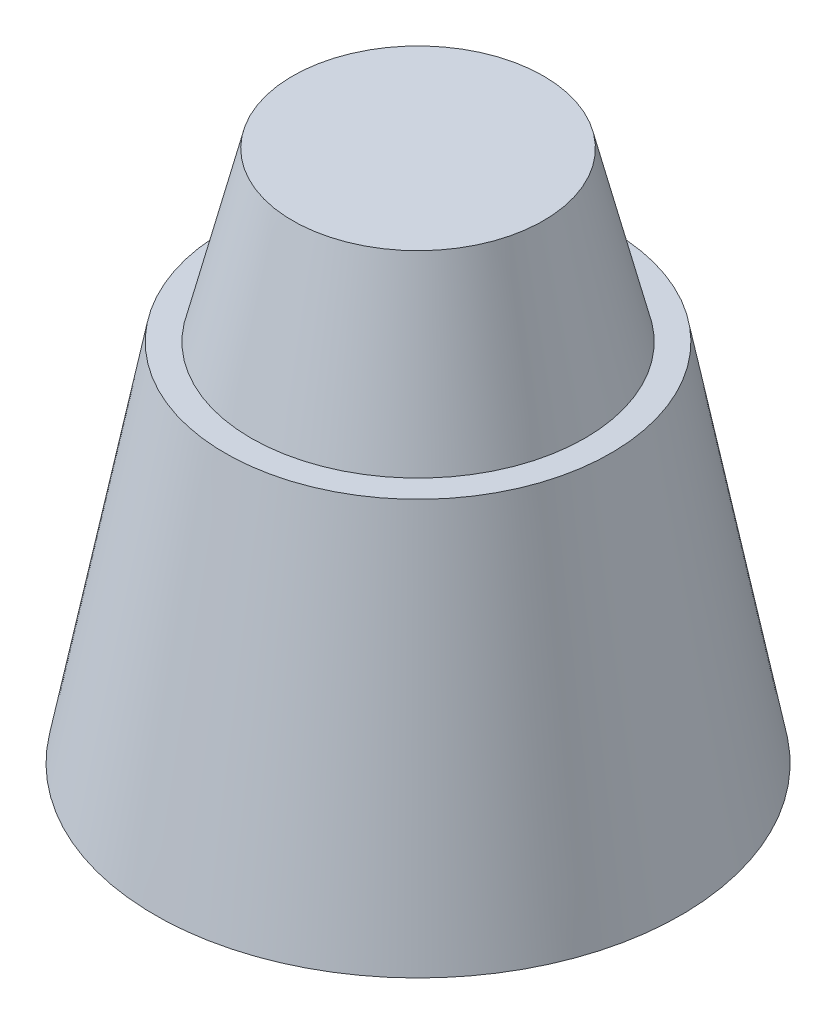
SolidWorks part; units mm, degrees
ref_plane "Front Plane" through (0, 0, 0) normal (0, 0, 1) x (1, 0, 0)
ref_plane "Top Plane" through (0, 0, 0) normal (0, 1, 0) x (1, 0, 0)
ref_plane "Right Plane" through (0, 0, 0) normal (1, 0, 0) x (0, 0, -1)
sketch "Sketch1" plane through (0, 0, 0) normal (0, 0, 1) x (1, 0, 0)
  line L0 (127, 271.5) -> (635, 271.5) construction
  line L1 (558.6307, 31.1336) -> (561.4806, 42.6223)
  line L2 (558.6307, 31.1336) -> (556.8495, 31.1336)
  line L3 (556.8495, 31.1336) -> (552.0404, 6.108)
  line L4 (561.4806, 42.6223) -> (570.0806, 42.6223)
  line L5 (570.0806, 42.6223) -> (570.0806, 6.108) construction
  line L6 (570.0806, 6.108) -> (552.0404, 6.108)
  line L7 (570.0806, 6.108) -> (570.0806, 42.6223)
revolve "Revolve1" add sketch "Sketch1" angle 360 about L7
sketch "Sketch3" plane through (0, 6.108, 0) normal (0, -1, 0) x (-1, 0, 0)
  circle A0 centre (-570.0806, 0) radius 12.27
extrude "Cut-Extrude1" cut sketch "Sketch3" against normal blind 10
fillet "Fillet1" radius 10 1 edges at (570.0806, 16.108, -12.27)
sketch "Sketch4" plane through (0, 16.108, 0) normal (0, -1, 0) x (-1, 0, 0)
  circle A0 centre (-570.0806, 0) radius 2.27
extrude "Cut-Extrude2" cut sketch "Sketch4" against normal blind 10
